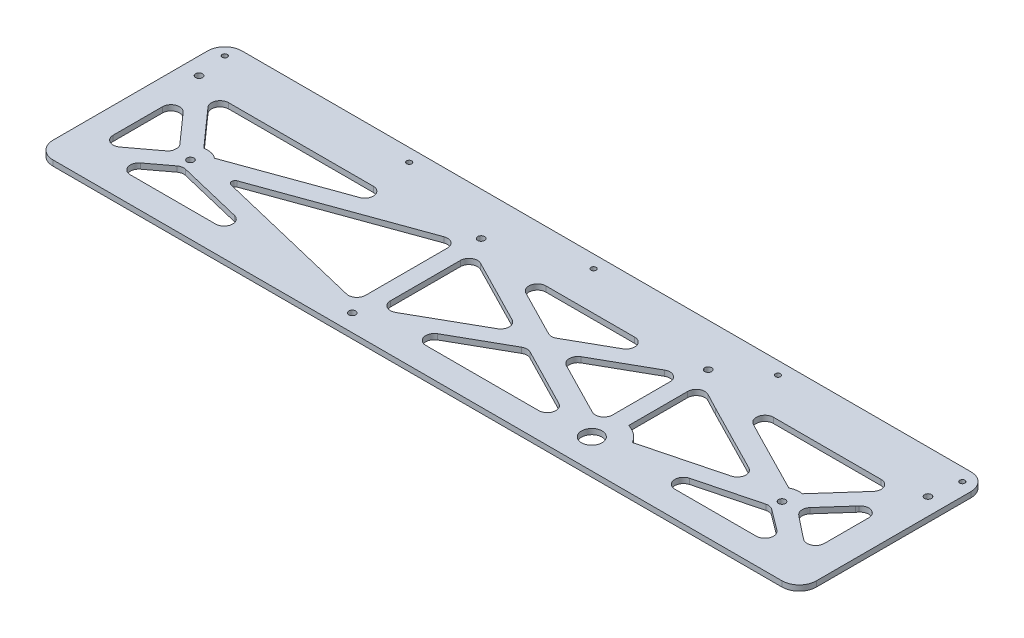
SolidWorks part; units mm, degrees
ref_plane "Front" through (0, 0, 0) normal (0, 0, 1) x (1, 0, 0)
ref_plane "Top" through (0, 0, 0) normal (0, 1, 0) x (1, 0, 0)
ref_plane "Right" through (0, 0, 0) normal (1, 0, 0) x (0, 0, -1)
sketch "Sketch1" plane through (0, 0, 0) normal (0, 1, 0) x (1, 0, 0)
  line L0 (-26.7996, 0) -> (-26.7996, 40)
  line L1 (-26.7996, 0) -> (417.7004, 0)
  line L2 (-26.7996, 0) -> (-26.7996, 110)
  line L3 (-26.7996, 110) -> (417.7004, 110)
  line L4 (417.7004, 0) -> (417.7004, 110)
  line L5 (-26.7996, 40) -> (23.2004, 40)
  line L6 (417.7004, 0) -> (417.7004, 40)
  line L7 (417.7004, 40) -> (367.7004, 40)
  line L8 (23.2004, 40) -> (103.2004, 40)
  line L9 (367.7004, 40) -> (191.7004, 40)
  line L10 (-26.7996, 110) -> (-26.7996, 85)
  line L11 (-26.7996, 85) -> (417.7004, 85)
  line L12 (-26.7996, 85) -> (-16.7996, 85)
  line L13 (417.7004, 85) -> (407.7004, 85)
  line L14 (103.2004, 40) -> (191.7004, 40)
  line L15 (147.4504, 40) -> (147.4504, 85)
  line L16 (279.7004, 40) -> (279.7004, 85)
  line L17 (147.4504, 40) -> (147.4504, 10)
  line L18 (-26.7996, 110) -> (-26.7996, 102.5)
  line L19 (-26.7996, 102.5) -> (417.7004, 102.5)
  line L20 (-26.7996, 102.5) -> (-19.2996, 102.5)
  line L21 (417.7004, 102.5) -> (410.2004, 102.5)
  line L22 (195.4504, 102.5) -> (410.2004, 102.5)
  line L23 (-19.2996, 102.5) -> (195.4504, 102.5)
  line L24 (417.7004, 0) -> (417.7004, 17.2282)
  line L25 (417.7004, 17.2282) -> (279.7004, 17.2282)
  circle A10 centre (367.7004, 40) radius 2
  circle A11 centre (23.2004, 40) radius 2
  circle A25 centre (-16.7996, 85) radius 2
  circle A26 centre (407.7004, 85) radius 2
  circle A27 centre (147.4504, 85) radius 2
  circle A28 centre (279.7004, 85) radius 2
  circle A29 centre (147.4504, 10) radius 2
  circle A30 centre (195.4504, 102.5) radius 1.5
  circle A31 centre (-19.2996, 102.5) radius 1.5
  circle A32 centre (410.2004, 102.5) radius 1.5
  circle A33 centre (302.8254, 102.5) radius 1.5
  circle A34 centre (88.0754, 102.5) radius 1.5
  circle A35 centre (279.7004, 17.2282) radius 6
  dimension "D3" = 40
  dimension "D7" = 80
  dimension "D8" = 176
  dimension "D9" = 25
  dimension "D11" = 10
  dimension "D12" = 30
  dimension "D13" = 7.5
  dimension "D14" = 7.5
  dimension "D16" = 17.2282
  dimension "D1" = 110
  dimension "D2" = 444.5
  dimension "D4" = 50
  dimension "D5" = 40
  dimension "D6" = 50
  dimension "D10" = 10
  dimension "D15" = 7.5
  dimension "D17" = 138
extrude "Boss-Extrude1" add sketch "Sketch1" along normal blind 3.175 contours A34 L23 A30 L22 A33 A32 L21 L4 L3 L10 L19 A31 | A34 L23 A31 L19 L2 L11 A25 A27 A28 A26 L13 L4 L21 A32 L22 A33 A30 | A27 L11 A25 L2 L5 A11 L8 L14 L15 | A28 L11 A27 L15 L14 L9 L16 | A28 L16 L9 A10 L7 L4 L13 A26 L11 | A35 L6 L7 A10 L9 L14 A29 L8 A11 L5 L0 L1 L4 region at (194.9445, 0, -20.0113) region at (60.3825, 0, -62.4913) region at (195.421, 0, -93.7571) region at (195.4504, 0, -106.2666) region at (348.6559, 0, -62.489) region at (213.5754, 0, -62.4771)
fillet "Fillet1" radius 10 4 edges at (417.7004, 1.5875, -110) (417.7004, 1.5875, 0) (-26.7996, 1.5875, 0) (-26.7996, 1.5875, -110)
sketch "Sketch2" plane through (0, 3.175, 0) normal (0, 1, 0) x (1, 0, 0)
  line L0 (23.2004, 40) -> (16.1294, 32.9289)
  line L1 (147.4504, 47.5) -> (152.4504, 47.5)
  line L2 (391.4375, 59.1782) -> (378.9401, 45.1187)
  line L3 (383.9634, 65.8218) -> (369.7169, 49.7946)
  line L4 (9732.2026, 3263.3975) -> (9728.9552, 3272.8555)
  line L5 (147.4504, 47.5) -> (142.4504, 47.5)
  line L6 (322.4478, 33.4546) -> (294.4087, 26.1989)
  line L7 (152.4504, 47.5) -> (152.4504, 67.9441)
  line L8 (-16.7996, 0) -> (407.7004, 0) construction
  line L9 (147.4504, 10) -> (147.4504, 0)
  line L10 (152.4504, 47.5) -> (152.4504, 27.2341)
  line L11 (142.4504, 47.5) -> (142.4504, 70.4046)
  line L12 (142.4504, 47.5) -> (142.4504, 22.7018)
  line L13 (147.4504, 10) -> (147.4504, 85)
  line L14 (147.4504, 85) -> (279.7004, 85)
  line L15 (279.7004, 85) -> (279.7004, 17.2282)
  line L16 (251.0087, 15) -> (185.2783, 15)
  line L17 (147.4504, 85) -> (-16.7996, 85)
  line L18 (-16.7996, 85) -> (23.2004, 40)
  line L19 (279.7004, 85) -> (407.7004, 85)
  line L20 (65.3254, 85) -> (65.3254, 80)
  line L21 (65.3254, 80) -> (5.4689, 80)
  line L22 (65.3254, 80) -> (89.687, 80)
  line L23 (190.2472, 80) -> (241.8726, 80)
  line L24 (322.713, 80) -> (385.432, 80)
  line L25 (279.7004, 51.1141) -> (274.7004, 51.1141)
  line L26 (279.7004, 51.1141) -> (284.7004, 51.1141)
  line L27 (274.7004, 51.1141) -> (274.7004, 34.284)
  line L28 (274.7004, 67.7659) -> (274.7004, 51.1141)
  line L29 (284.7004, 68.0769) -> (284.7004, 51.1141)
  line L30 (86.4989, 29.8603) -> (47.5547, 39.2634)
  line L31 (86.4989, 29.8603) -> (136.2769, 17.8415)
  line L32 (3.2004, 62.5) -> (6.9375, 65.8218)
  line L33 (23.2004, 40) -> (147.4504, 10)
  line L34 (85.3254, 25) -> (86.4989, 29.8603)
  line L35 (284.7004, 51.1141) -> (284.7004, 33.7148)
  line L36 (279.7004, 17.2282) -> (367.7004, 40)
  line L37 (367.7004, 40) -> (407.7004, 85)
  line L38 (383.9634, 65.8218) -> (389.169, 71.6782)
  line L39 (383.9634, 65.8218) -> (387.7004, 62.5)
  line L40 (391.4375, 59.1782) -> (387.7004, 62.5)
  line L41 (391.4375, 59.1782) -> (392.3703, 60.2665)
  line L42 (322.4478, 33.4546) -> (323.7004, 28.6141)
  line L43 (324.953, 23.7735) -> (323.7004, 28.6141)
  line L44 (329.0765, 24.8406) -> (364.2961, 33.9544)
  line L45 (322.4478, 33.4546) -> (340.0585, 38.0118)
  line L46 (324.953, 23.7735) -> (296.9139, 16.5178)
  line L47 (3.2004, 62.5) -> (-0.5366, 59.1782)
  line L48 (-0.5366, 59.1782) -> (12.2431, 44.801)
  line L49 (-0.5366, 59.1782) -> (-3.0625, 62.0198)
  line L50 (6.9375, 65.8218) -> (21.1839, 49.7946)
  line L51 (6.9375, 65.8218) -> (1.7318, 71.6782)
  line L52 (85.3254, 25) -> (84.1182, 20)
  line L53 (84.1182, 20) -> (26.4566, 33.9223)
  line L54 (30.3293, 32.9872) -> (63.9883, 24.8603)
  line L55 (330.3291, 15) -> (377.7004, 15)
  line L56 (407.7004, 10) -> (402.7004, 10)
  line L57 (401.1667, 31.1503) -> (401.1667, 57.0127)
  line L58 (367.7004, 40) -> (407.7004, 10)
  line L59 (390.7004, 29) -> (384.7004, 21)
  line L60 (23.2004, 40) -> (147.4504, 85)
  line L61 (83.5146, 67.5) -> (87.1363, 57.5)
  line L62 (83.5146, 67.5) -> (29.3522, 47.8839)
  line L63 (83.5146, 67.5) -> (91.3614, 70.2887)
  line L64 (87.1363, 57.5) -> (135.7478, 75.1058)
  line L65 (87.1363, 57.5) -> (47.3431, 43.088)
  line L66 (279.7004, 85) -> (367.7004, 40)
  line L67 (326.2572, 67.5) -> (321.1436, 57.5)
  line L68 (301.2048, 67.696) -> (341.0824, 47.304)
  line L69 (326.2572, 67.5) -> (320.3935, 70.5706)
  line L70 (326.2572, 67.5) -> (362.8903, 48.7672)
  line L71 (147.4504, 85) -> (279.7004, 17.2282)
  line L72 (218.7979, 42.1248) -> (253.2889, 24.4498)
  line L73 (216.1377, 56.1141) -> (211.0132, 46.1141)
  line L74 (197.4862, 53.046) -> (159.7307, 72.3939)
  line L75 (215.0566, 56.6681) -> (187.9669, 70.5502)
  line L76 (236.3682, 45.7469) -> (267.4201, 29.8343)
  line L77 (147.4504, 10) -> (279.7004, 85)
  line L78 (211.1089, 51.8493) -> (216.0419, 43.1507)
  line L79 (219.799, 56.7661) -> (244.3347, 70.6483)
  line L80 (236.1863, 54.5484) -> (267.2382, 72.1176)
  line L81 (197.6682, 44.2445) -> (159.9126, 22.8824)
  line L82 (214.0554, 42.0268) -> (182.8161, 24.3517)
  line L83 (-16.7996, 85) -> (-16.7996, 15)
  line L84 (-11.7996, 10) -> (147.4504, 10)
  line L85 (147.4504, 10) -> (402.7004, 10)
  line L86 (407.7004, 85) -> (407.7004, 15)
  line L87 (-16.7996, 10) -> (-16.7996, 15)
  line L88 (-16.7996, 10) -> (-11.7996, 10)
  line L89 (13.2004, 15) -> (62.8148, 15)
  line L90 (-11.7996, 30) -> (-11.7996, 58.698)
  line L91 (390.7004, 29) -> (379.559, 37.8883)
  line L92 (388.7004, 18) -> (380.7004, 24)
  line L93 (380.7004, 24) -> (368.5487, 33.1138)
  line L94 (390.7004, 29) -> (393.1667, 27.1503)
  line L95 (23.2004, 40) -> (-16.7996, 10)
  line L96 (0.2004, 29) -> (6.2004, 21)
  line L97 (11.506, 37.4792) -> (-3.7996, 26)
  line L98 (10.2004, 24) -> (22.2831, 33.062)
  line L100 (6.2004, 21) -> (-8.4662, 10)
  line L101 (301.2048, 67.696) -> (292.0202, 72.5062)
  arc A0 (-3.0625, 62.0198) -> (-11.7996, 58.698) centre (-6.7996, 58.698) ccw
  arc A3 (219.799, 56.7661) -> (215.0566, 56.6681) centre (217.3369, 61.1179) cw
  arc A4 (241.8726, 80) -> (244.3347, 70.6483) centre (241.8726, 75) cw
  circle A5 centre (147.4504, 85) radius 10
  arc A7 (190.2472, 80) -> (187.9669, 70.5502) centre (190.2472, 75) ccw
  circle A8 centre (279.7004, 85) radius 10
  arc A10 (5.4689, 80) -> (1.7318, 71.6782) centre (5.4689, 75) ccw
  arc A11 (89.687, 80) -> (91.3614, 70.2887) centre (89.687, 75) cw
  arc A12 (135.7478, 75.1058) -> (142.4504, 70.4046) centre (137.4504, 70.4046) cw
  arc A13 (142.4504, 22.7018) -> (136.2769, 17.8415) centre (137.4504, 22.7018) cw
  arc A14 (47.5547, 39.2634) -> (47.3431, 43.088) centre (48.0241, 41.2075) cw
  arc A15 (159.9126, 22.8824) -> (152.4504, 27.2341) centre (157.4504, 27.2341) cw
  arc A16 (197.6682, 44.2445) -> (197.4862, 53.046) centre (195.206, 48.5962) ccw
  arc A17 (159.7307, 72.3939) -> (152.4504, 67.9441) centre (157.4504, 67.9441) ccw
  arc A18 (274.7004, 34.284) -> (267.4201, 29.8343) centre (269.7004, 34.284) cw
  circle A19 centre (147.4504, 10) radius 10
  circle A21 centre (23.2004, 40) radius 10
  circle A22 centre (9732.2026, 3263.3975) radius 10
  circle A24 centre (-16.7996, 85) radius 10
  circle A25 centre (407.7004, 85) radius 10
  circle A26 centre (279.7004, 17.2282) radius 17.2282
  circle A27 centre (367.7004, 40) radius 10
  arc A28 (236.1863, 54.5484) -> (236.3682, 45.7469) centre (238.6485, 50.1967) ccw
  arc A29 (274.7004, 67.7659) -> (267.2382, 72.1176) centre (269.7004, 67.7659) ccw
  arc A30 (341.0824, 47.304) -> (340.0585, 38.0118) centre (338.8059, 42.8523) cw
  arc A31 (322.713, 80) -> (320.3935, 70.5706) centre (322.713, 75) ccw
  arc A32 (292.0202, 72.5062) -> (284.7004, 68.0769) centre (289.7004, 68.0769) ccw
  arc A33 (385.432, 80) -> (389.169, 71.6782) centre (385.432, 75) cw
  arc A34 (379.559, 37.8883) -> (378.9401, 45.1187) centre (382.6772, 41.7969) cw
  arc A35 (401.1667, 57.0127) -> (392.3703, 60.2665) centre (396.1667, 57.0127) ccw
  arc A36 (401.1667, 31.1503) -> (393.1667, 27.1503) centre (396.1667, 31.1503) cw
  arc A37 (377.7004, 15) -> (380.7004, 24) centre (377.7004, 20) ccw
  arc A38 (218.7979, 42.1248) -> (214.0554, 42.0268) centre (216.5176, 37.675) ccw
  arc A39 (182.8161, 24.3517) -> (185.2783, 15) centre (185.2783, 20) ccw
  arc A40 (251.0087, 15) -> (253.2889, 24.4498) centre (251.0087, 20) ccw
  arc A41 (11.506, 37.4792) -> (12.2431, 44.801) centre (8.506, 41.4792) ccw
  arc A42 (-3.7996, 26) -> (-11.7996, 30) centre (-6.7996, 30) cw
  arc A43 (13.2004, 15) -> (10.2004, 24) centre (13.2004, 20) cw
  arc A44 (62.8148, 15) -> (63.9883, 24.8603) centre (62.8148, 20) ccw
  arc A45 (329.0765, 24.8406) -> (330.3291, 15) centre (330.3291, 20) ccw
  arc A46 (-11.7996, 10) -> (-16.7996, 15) centre (-11.7996, 15) cw
  arc A47 (402.7004, 10) -> (407.7004, 15) centre (402.7004, 15) ccw
  arc A48 (26.4566, 33.9223) -> (22.2831, 33.062) centre (25.2831, 29.062) ccw
  arc A49 (368.5487, 33.1138) -> (364.2961, 33.9544) centre (365.5487, 29.1138) ccw
  point P84 (213.5754, 13.6141)
  point P91 (85.3254, 62.5)
  point P98 (323.7004, 62.5)
  point P100 (321.1436, 57.5)
  point P106 (213.5754, 51.1141)
  point P109 (213.5754, 47.5)
  point P114 (211.0132, 46.1141)
  point P115 (213.5754, 47.5)
  point P128 (387.7004, 25)
  point P135 (3.2004, 25)
  point P136 (0.2004, 29)
  point P173 (384.7004, 21)
  dimension "D7" = 5
  dimension "D2" = 5
  dimension "D9" = 5
  dimension "D20" = 10
  dimension "D22" = 5
  dimension "D16" = 5
  dimension "D17" = 5
  dimension "D23" = 5
  dimension "D24" = 5
  dimension "D25" = 5
  dimension "D26" = 5
  dimension "D27" = 5
  dimension "D28" = 2
  dimension "D29" = 5
  dimension "D30" = 5
  dimension "D31" = 5
  dimension "D32" = 5
  dimension "D33" = 5
  dimension "D34" = 5
  dimension "D35" = 5
  dimension "D36" = 5
  dimension "D37" = 5
  dimension "D38" = 5
  dimension "D39" = 5
  dimension "D40" = 5
  dimension "D13" = 5
  dimension "D41" = 5
  dimension "D42" = 5
  dimension "D43" = 5
  dimension "D44" = 5
  dimension "D45" = 5
  dimension "D19" = 5
  dimension "D18" = 5
  dimension "D46" = 5
  dimension "D10" = 5
  dimension "D47" = 5
  dimension "D48" = 5
  dimension "D49" = 5
  dimension "D50" = 5
  dimension "D1" = 10
  dimension "D6" = 5
  dimension "D3" = 5
  dimension "D4" = 5
  dimension "D5" = 5
  dimension "D8" = 5
  dimension "D11" = 5
  dimension "D12" = 5
  dimension "D14" = 10
  dimension "D15" = 10
  dimension "D21" = 10
extrude "Cut-Extrude1" cut sketch "Sketch2" against normal blind 10 contours A21 L62 L63 A11 L22 L21 A10 L51 L50 | A42 L97 A41 A21 L48 L49 A0 L90 | L89 A44 L53 A21 L98 A43 | L53 A48 L98 A21 | A14 L30 L31 A13 L12 L11 A12 L64 L65 | L74 A17 L7 L10 A15 L81 A16 | L23 A7 L75 A3 L79 A4 | L16 A40 L72 A38 L82 A39 | L28 A29 L80 A28 L76 A18 A26 L27 | L101 A32 L29 L35 A26 L6 L45 A30 L68 | A18 A26 | A33 L24 A31 L69 L70 A27 L3 L38 | L44 A45 L55 A37 L93 A27 | A36 L57 A35 L41 L2 A34 L91 L94 | L93 A49 L44 A45 L55 A37 region at (36.9296, 3.175, -22.103) region at (24.7671, 3.175, -31.9692) region at (43.3698, 3.175, -68.2948) region at (-2.1335, 3.175, -43.7439) region at (108.6161, 3.175, -44.8774) region at (170.1476, 3.175, -47.8878) region at (271.5408, 3.175, -31.1451) region at (259.0948, 3.175, -51.0247) region at (307.4149, 3.175, -47.5805) region at (356.407, 3.175, -68.4868) region at (392.0855, 3.175, -43.601) region at (354.9862, 3.175, -22.1013) region at (217.8598, 3.175, -25.0975) region at (216.2593, 3.175, -71.0892)
equation "\"width\"=8.66025"
equation "\"supw\"=5"
